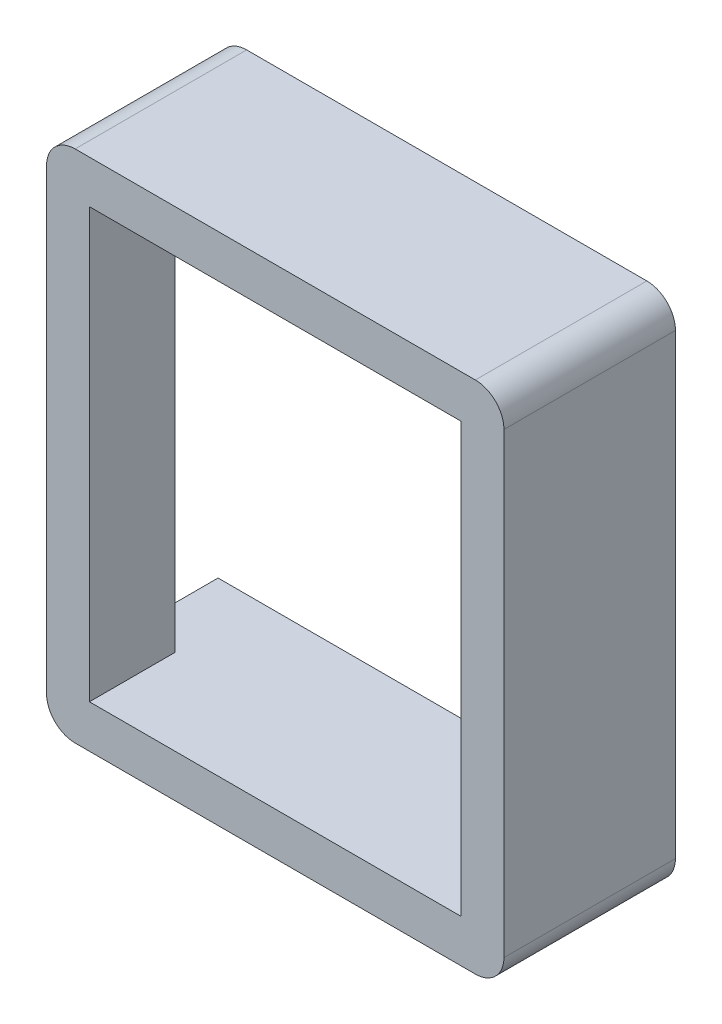
SolidWorks part; units mm, degrees
ref_plane "前视基准面" through (0, 0, 0) normal (0, 0, 1) x (1, 0, 0)
ref_plane "上视基准面" through (0, 0, 0) normal (0, 1, 0) x (1, 0, 0)
ref_plane "右视基准面" through (0, 0, 0) normal (1, 0, 0) x (0, 0, -1)
sketch "草图1" plane through (0, 0, 0) normal (0, 0, 1) x (1, 0, 0)
  line L1 (-70, -90) -> (70, -90)
  line L2 (-80, -80) -> (-80, 80)
  line L3 (-70, 90) -> (70, 90)
  line L4 (80, -80) -> (80, 80)
  line L5 (-80, -90) -> (80, 90) construction
  line L6 (-80, 90) -> (80, -90) construction
  arc A0 (70, -90) -> (80, -80) centre (70, -80) ccw
  arc A1 (-70, -90) -> (-80, -80) centre (-70, -80) cw
  arc A2 (-80, 80) -> (-70, 90) centre (-70, 80) cw
  arc A3 (70, 90) -> (80, 80) centre (70, 80) cw
  point P0 (0, 0)
  dimension "D3" = 10
  dimension "D1" = 180
  dimension "D2" = 160
extrude "凸台-拉伸1" add sketch "草图1" along normal blind 60
sketch "草图5" plane through (-80, 0, 0) normal (-1, 0, 0) x (0, 0, 1)
  line L0 (0, 0) -> (30, 0) construction
  line L1 (0, -75) -> (0, 75)
  line L2 (0, 80) -> (0, -80) construction
  line L3 (0, 75) -> (30, 75)
  line L4 (30, 75) -> (30, -75)
  line L5 (0, -75) -> (30, -75)
  point P8 (28.845, 0)
  dimension "D1" = 75
  dimension "D2" = 30
extrude "切除-拉伸2" cut sketch "草图5" against normal offset from surface 10 and the other way through all up to face at (80, 0, 30)
sketch "草图6" plane through (0, 0, 60) normal (0, 0, 1) x (1, 0, 0)
  line L1 (-65, -75) -> (65, -75)
  line L2 (-65, -75) -> (-65, 75)
  line L3 (-65, 75) -> (65, 75)
  line L4 (65, -75) -> (65, 75)
  line L5 (-65, -75) -> (65, 75) construction
  line L6 (-65, 75) -> (65, -75) construction
  point P0 (0, 0)
  dimension "D1" = 150
  dimension "D2" = 130
extrude "切除-拉伸3" cut sketch "草图6" against normal through all both and the other way through all
